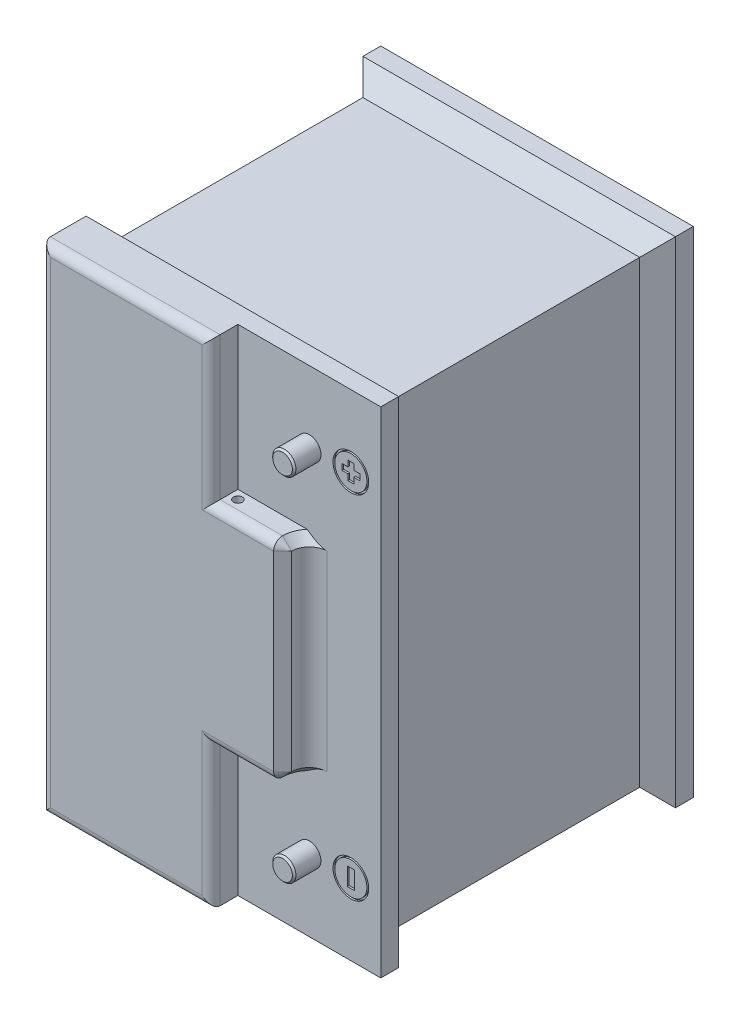
SolidWorks part; units mm, degrees
material "ABS PC"
ref_plane "Plan de face" through (0, 0, 0) normal (0, 0, 1) x (1, 0, 0)
ref_plane "Plan de dessus" through (0, 0, 0) normal (0, 1, 0) x (1, 0, 0)
ref_plane "Plan de droite" through (0, 0, 0) normal (1, 0, 0) x (0, 0, -1)
sketch "Esquisse1" plane through (0, 0, 0) normal (0, 0, 1) x (1, 0, 0)
  line L1 (0, 0) -> (175, 0)
  line L2 (0, 0) -> (0, 277)
  line L3 (0, 277) -> (175, 277)
  line L4 (175, 0) -> (175, 277)
  dimension "D1" = 277
  dimension "D2" = 175
extrude "Boss.-Extru.2" add sketch "Esquisse1" along normal blind 190
sketch "Esquisse2" plane through (0, 0, 190) normal (0, 0, 1) x (1, 0, 0)
  line L1 (175, 0) -> (95, 0)
  line L2 (175, 0) -> (175, 80)
  line L3 (175, 80) -> (95, 80)
  line L4 (95, 0) -> (95, 80)
  line L5 (175, 277) -> (95, 277)
  line L6 (175, 277) -> (175, 197)
  line L7 (175, 197) -> (95, 197)
  line L8 (95, 277) -> (95, 197)
  dimension "D1" = 80
extrude "Enlèv. mat.-Extru.2" cut sketch "Esquisse2" against normal blind 15
sketch "Esquisse6" plane through (0, 0, 175) normal (0, 0, 1) x (1, 0, 0)
  line L0 (175, 0) -> (175, 80) construction
  line L1 (95, 0) -> (175, 0) construction
  line L2 (175, 80) -> (175, 197) construction
  line L3 (175, 138.5) -> (110.2131, 138.5) construction
  circle A0 centre (135, 40) radius 6.5
  circle A1 centre (135, 237) radius 6.5
  point P2 (175, 40)
  dimension "D1" = 40
  dimension "D2" = 13
  dimension "D3" = 40
extrude "Boss.-Extru.4" add sketch "Esquisse6" along normal blind 15
chamfer "Chanfrein2" distance 1 angle 45 2 edges at (141.5, 40, 190) (128.5, 237, 190)
sketch "Esquisse12" plane through (0, 0, 0) normal (0, 0, -1) x (-1, 0, 0)
  line L0 (-175, 0) -> (-175, 277) construction
  line L1 (-165, 267) -> (-10, 267)
  line L2 (-165, 267) -> (-165, 10)
  line L3 (-165, 10) -> (-10, 10)
  line L4 (-10, 267) -> (-10, 10)
  line L5 (0, 277) -> (0, 0) construction
  line L6 (-175, 277) -> (0, 277) construction
  line L7 (0, 0) -> (-175, 0) construction
  dimension "D1" = 10
  dimension "D2" = 10
  dimension "D3" = 10
  dimension "D4" = 10
extrude "Enlèv. mat.-Extru.5" cut sketch "Esquisse12" against normal blind 155 from offset 10 flip side to cut offset against normal yes
chamfer "Chanfrein5" distance 10 angle 45 4 edges at (87.5, 10, 10) (165, 138.5, 10) (87.5, 267, 10) (10, 138.5, 10)
fillet "Congé1" radius 5 8 edges at (135, 80, 190) (95, 40, 190) (47.5, 0, 190) (0, 138.5, 190) (47.5, 277, 190) (95, 237, 190) (135, 197, 190) (175, 138.5, 190)
sketch "Esquisse13" plane through (0, 80, 0) normal (0, -1, 0) x (1, 0, 0)
  line L1 (145, 175) -> (175, 175)
  line L2 (175, 175) -> (175, 190)
  line L7 (175, 175) -> (95, 175) construction
  line L12 (95, 175) -> (95, 185) construction
  line L13 (135, 185) -> (135, 190)
  line L14 (135, 190) -> (175, 190)
  line L16 (90, 190) -> (170, 190) construction
  line L17 (175, 185) -> (95, 185) construction
  circle A0 centre (100, 180) radius 2.5
  arc A2 (135, 185) -> (145, 175) centre (145, 185) ccw
  point P6 (135, 185)
  dimension "D1" = 5
  dimension "D3" = 5
  dimension "D4" = 45
  dimension "D5" = 10
  dimension "D2" = 5
extrude "Enlèv. mat.-Extru.10" cut sketch "Esquisse13" against normal up to next
chamfer "Chanfrein8" distance 5 angle 45 5 edges at (137.9289, 197, 177.9289) (137.9289, 80, 177.9289) (135, 195.5355, 188.5355) (135, 81.4645, 188.5355) (135, 138.5, 190)
fillet "Congé3" radius 10 4 edges at (165, 138.5, 165) (87.5, 267, 165) (10, 138.5, 165) (87.5, 10, 165)
sketch "Esquisse14" plane through (0, 0, 175) normal (0, 0, 1) x (1, 0, 0)
  line L0 (175, 0) -> (175, 277) construction
  line L1 (141.5, 40) -> (175, 40) construction
  line L2 (95, 0) -> (175, 0) construction
  line L8 (145, 138.5) -> (175, 138.5) construction
  line L9 (145, 192) -> (145, 85) construction
  circle A0 centre (158.25, 40) radius 10
  circle A1 centre (158.25, 40) radius 9
  circle A8 centre (135, 40) radius 6.5 construction
  circle A9 centre (158.25, 237) radius 9
  circle A10 centre (158.25, 237) radius 10
  point P6 (175, 40)
  point P9 (141.5, 40)
  point P13 (158.25, 40)
  dimension "D1" = 20
  dimension "D2" = 18
  dimension "D3" = 40
extrude "Enlèv. mat.-Extru.11" cut sketch "Esquisse14" against normal blind 1
sketch "Esquisse15" plane through (0, 0, 175) normal (0, 0, 1) x (1, 0, 0)
  line L0 (156.25, 45) -> (160.25, 35) construction
  line L1 (156.25, 35) -> (160.25, 35)
  line L2 (156.25, 35) -> (156.25, 45)
  line L3 (156.25, 45) -> (160.25, 45)
  line L4 (160.25, 35) -> (160.25, 45)
  line L5 (156.5833, 235.3333) -> (153.25, 235.3333)
  line L6 (153.25, 235.3333) -> (153.25, 238.6667)
  line L7 (153.25, 238.6667) -> (156.5833, 238.6667)
  line L8 (156.5833, 238.6667) -> (156.5833, 242)
  line L9 (156.5833, 242) -> (159.9167, 242)
  line L10 (159.9167, 242) -> (159.9167, 238.6667)
  line L11 (159.9167, 238.6667) -> (163.25, 238.6667)
  line L12 (163.25, 238.6667) -> (163.25, 235.3333)
  line L13 (163.25, 235.3333) -> (159.9167, 235.3333)
  line L14 (159.9167, 235.3333) -> (159.9167, 232)
  line L15 (159.9167, 232) -> (156.5833, 232)
  line L16 (156.5833, 232) -> (156.5833, 235.3333)
  line L17 (156.5833, 238.6667) -> (159.9167, 235.3333) construction
  circle A0 centre (158.25, 40) radius 9 construction
  circle A1 centre (158.25, 237) radius 9 construction
  point P4 (158.25, 40)
  point P20 (158.25, 237)
  dimension "D1" = 4
  dimension "D2" = 10
  dimension "D3" = 10
extrude "Enlèv. mat.-Extru.12" cut sketch "Esquisse15" against normal blind 1
